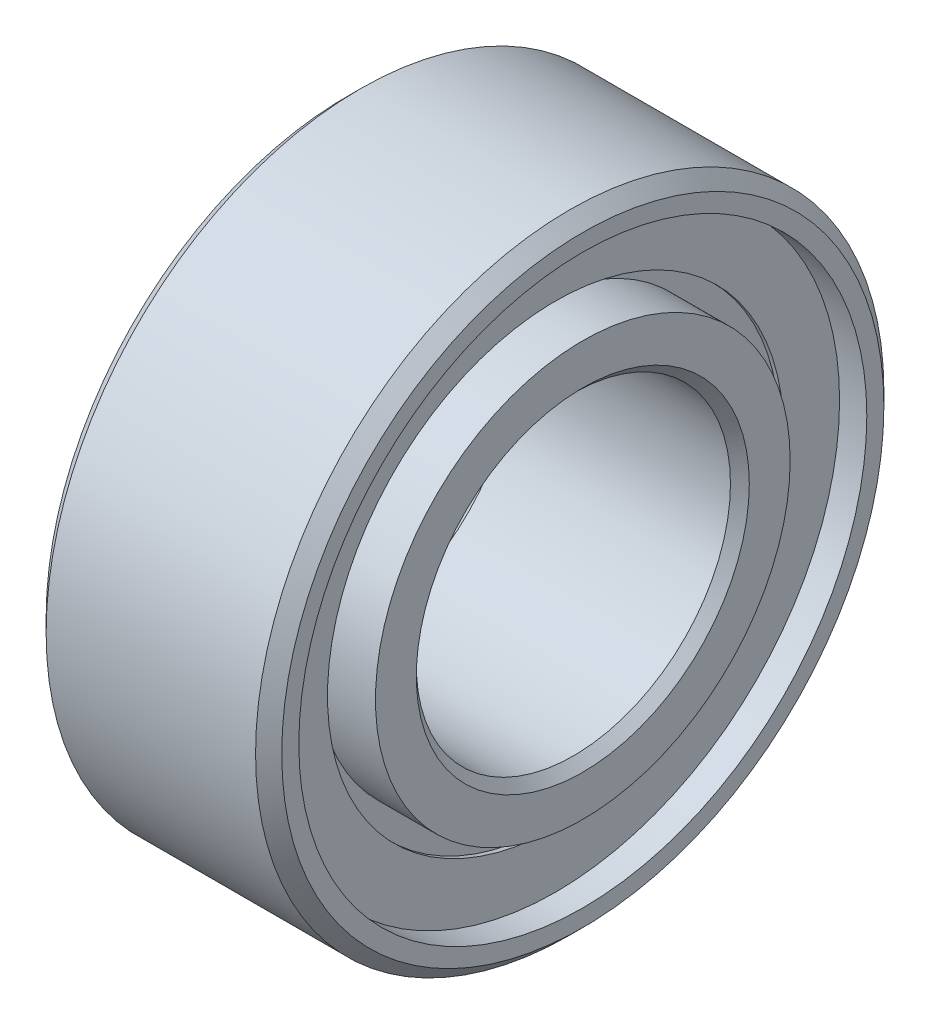
SolidWorks part; units mm, degrees
ref_plane "Front Plane" through (0, 0, 0) normal (0, 0, 1) x (1, 0, 0)
ref_plane "Top Plane" through (0, 0, 0) normal (0, 1, 0) x (1, 0, 0)
ref_plane "Right Plane" through (0, 0, 0) normal (1, 0, 0) x (0, 0, -1)
sketch "Sketch1" plane through (0, 0, 0) normal (0, 0, 1) x (1, 0, 0)
  line L0 (-2.3812, 3.3655) -> (-2.1907, 3.175)
  line L1 (-2.1907, 3.175) -> (2.1907, 3.175)
  line L2 (2.1907, 3.175) -> (2.3812, 3.3655)
  line L3 (2.3812, 3.3655) -> (2.3812, 4.191)
  line L4 (2.3812, 4.191) -> (1.1906, 4.191)
  line L5 (1.1906, 4.191) -> (1.1906, 5.7404)
  line L6 (1.1906, 5.7404) -> (1.7413, 5.7404)
  line L7 (1.7413, 5.7404) -> (1.7413, 4.6101)
  line L8 (1.7413, 4.6101) -> (1.8306, 4.6101)
  line L9 (1.8306, 4.6101) -> (1.8306, 5.7404)
  line L10 (1.8306, 5.7404) -> (2.3812, 5.7404)
  line L11 (2.3812, 5.7404) -> (2.3812, 6.0854)
  line L12 (2.3812, 6.0854) -> (2.1167, 6.35)
  line L13 (2.1167, 6.35) -> (-2.1167, 6.35)
  line L14 (-2.1167, 6.35) -> (-2.3812, 6.0854)
  line L15 (-2.3812, 6.0854) -> (-2.3812, 5.7404)
  line L16 (-2.3812, 5.7404) -> (-1.8306, 5.7404)
  line L17 (-1.8306, 5.7404) -> (-1.8306, 4.6101)
  line L18 (-1.8306, 4.6101) -> (-1.7413, 4.6101)
  line L19 (-1.7413, 4.6101) -> (-1.7413, 5.7404)
  line L20 (-1.7413, 5.7404) -> (-1.1906, 5.7404)
  line L21 (-1.1906, 5.7404) -> (-1.1906, 4.191)
  line L22 (-1.1906, 4.191) -> (-2.3812, 4.191)
  line L23 (-2.3812, 4.191) -> (-2.3812, 3.3655)
  line L24 (-2.3812, 0) -> (2.3812, 0) construction
revolve "Revolve1" add sketch "Sketch1" angle 360 about L24 reverse direction yes
